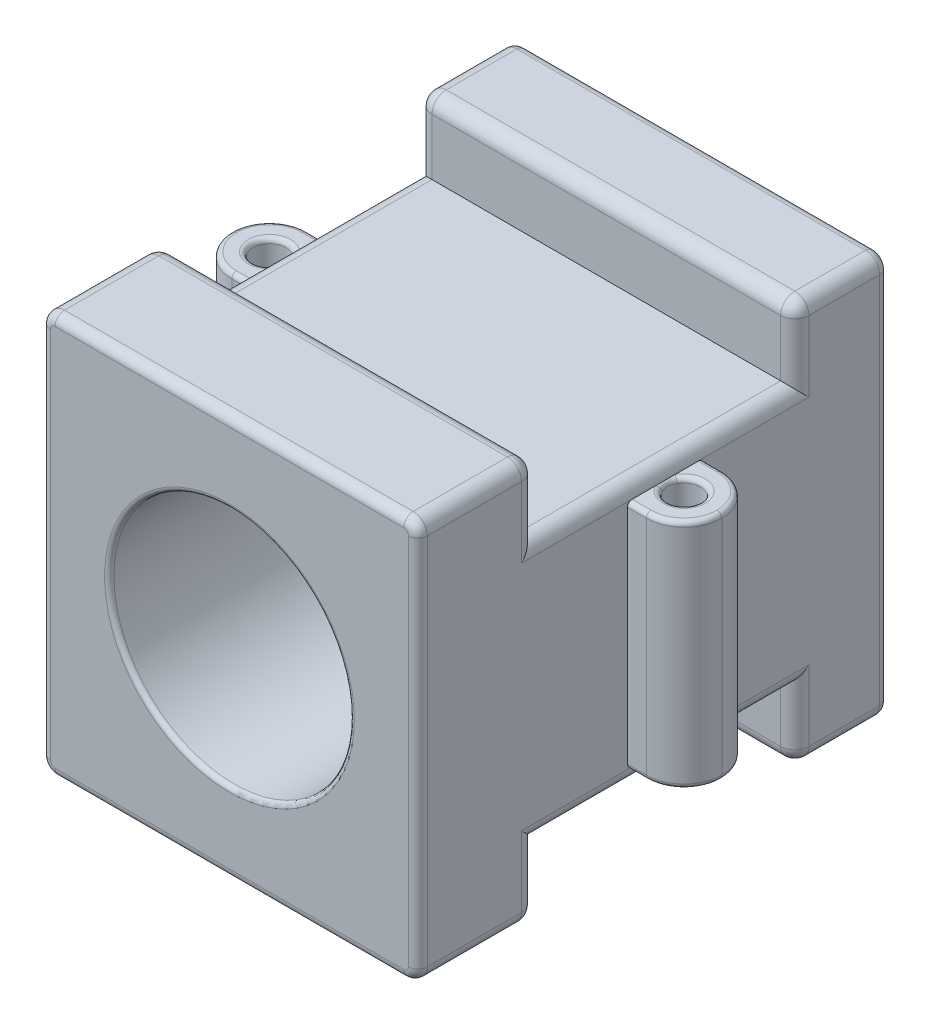
SolidWorks part; units mm, degrees
ref_plane "Plan de face" through (0, 0, 0) normal (0, 0, 1) x (1, 0, 0)
ref_plane "Plan de dessus" through (0, 0, 0) normal (0, 1, 0) x (1, 0, 0)
ref_plane "Plan de droite" through (0, 0, 0) normal (1, 0, 0) x (0, 0, -1)
sketch "Esquisse1" plane through (0, 0, 0) normal (0, 0, 1) x (1, 0, 0)
  line L1 (-40, 42.6) -> (40, 42.6)
  line L2 (-40, 42.6) -> (-40, -42.6)
  line L3 (-40, -42.6) -> (40, -42.6)
  line L4 (40, 42.6) -> (40, -42.6)
  line L5 (-40, 42.6) -> (40, -42.6) construction
  line L6 (-40, -42.6) -> (40, 42.6) construction
  point P0 (0, 0)
  dimension "D1" = 85.2
  dimension "D2" = 80
extrude "Boss.-Extru.1" add sketch "Esquisse1" along normal blind 100
sketch "Esquisse2" plane through (-40, 0, 0) normal (-1, 0, 0) x (0, 0, 1)
  line L0 (0, 0) -> (100, 0) construction
  line L1 (100, 42.6) -> (100, -42.6) construction
  line L2 (50, 0) -> (50, 42.6) construction
  line L3 (100, 42.6) -> (0, 42.6) construction
  line L4 (50, 42.6) -> (50, -42.6) construction
  line L5 (100, -42.6) -> (0, -42.6) construction
  line L6 (0, 42.6) -> (0, -42.6) construction
  line L7 (75, 42.6) -> (20, 42.6)
  line L8 (75, 42.6) -> (75, 27.6)
  line L9 (75, 27.6) -> (20, 27.6)
  line L10 (20, 42.6) -> (20, 27.6)
  line L12 (20, -42.6) -> (75, -42.6)
  line L13 (20, -42.6) -> (20, -27.6)
  line L14 (20, -27.6) -> (75, -27.6)
  line L15 (75, -42.6) -> (75, -27.6)
  dimension "D1" = 25
  dimension "D2" = 20
  dimension "D3" = 15
  dimension "D4" = 20
  dimension "D5" = 25
  dimension "D6" = 15
  dimension "D7" = 55
extrude "Enlèv. mat.-Extru.1" cut sketch "Esquisse2" against normal blind 100
fillet "Congé1" radius 3 4 edges at (0, -42.6, 75) (0, -42.6, 20) (0, 42.6, 75) (0, 42.6, 20)
fillet "Congé2" radius 2 4 edges at (40, 0, 0) (0, -42.6, 0) (-40, 0, 0) (0, 42.6, 0)
fillet "Congé3" radius 2 4 edges at (0, -42.6, 100) (-40, 0, 100) (0, 42.6, 100) (40, 0, 100)
fillet "Congé4" radius 3 36 edges at (-39.4142, -42.0142, 99.4142) (-39.4142, 42.0142, 99.4142) (39.4142, 42.0142, 99.4142) (39.4142, -42.0142, 99.4142) (-39.4142, -42.0142, 0.5858) (-39.4142, 42.0142, 0.5858) (39.4142, 42.0142, 0.5858) (39.4142, -42.0142, 0.5858) (40, -42.6, 9.5) (40, -41.7213, 19.1213) (40, 42.6, 9.5) (40, 41.7213, 19.1213) (-40, 42.6, 9.5) (-40, 41.7213, 19.1213) (-40, -42.6, 9.5) (-40, -41.7213, 19.1213) (40, -42.6, 88) (40, -41.7213, 75.8787) (40, 42.6, 88) (40, 41.7213, 75.8787) (-40, 42.6, 88) (-40, 41.7213, 75.8787) (-40, -42.6, 88) (-40, -41.7213, 75.8787) (40, -33.6, 20) (40, 33.6, 20) (40, 27.6, 47.5) (-40, 33.6, 20) (-40, -33.6, 20) (40, -27.6, 47.5) (40, -33.6, 75) (40, 33.6, 75) (-40, 33.6, 75) (-40, -33.6, 75) (-40, -27.6, 47.5) (-40, 27.6, 47.5)
sketch "Esquisse3" plane through (0, 0, 0) normal (0, 0, -1) x (-1, 0, 0)
  circle A0 centre (0, 0) radius 25.5
  dimension "D1" = 51
extrude "Enlèv. mat.-Extru.3" cut sketch "Esquisse3" against normal blind 100
sketch "Esquisse5" plane through (40, 0, 0) normal (1, 0, 0) x (0, 0, -1)
  line L1 (-78, 24.6) -> (-17, 24.6)
  line L2 (-78, 24.6) -> (-78, -24.6)
  line L3 (-78, -24.6) -> (-17, -24.6)
  line L4 (-17, 24.6) -> (-17, -24.6)
extrude "Boss.-Extru.2" add sketch "Esquisse5" along normal blind 20
sketch "Esquisse7" plane through (0, -24.6, 0) normal (0, -1, 0) x (1, 0, 0)
  line L0 (60, 78) -> (60, 17) construction
  line L1 (40, 78) -> (60, 78)
  line L2 (40, 78) -> (40, 68)
  line L3 (40, 68) -> (60, 68)
  line L4 (60, 78) -> (60, 68)
  line L5 (40, 78) -> (40, 17) construction
  line L6 (60, 17) -> (40, 17)
  line L7 (60, 17) -> (60, 27)
  line L8 (60, 27) -> (40, 27)
  line L9 (40, 17) -> (40, 27)
  dimension "D1" = 10
  dimension "D2" = 10
extrude "Enlèv. mat.-Extru.4" cut sketch "Esquisse7" against normal blind 60
sketch "Esquisse8" plane through (0, -24.6, 0) normal (0, -1, 0) x (1, 0, 0)
  line L0 (60, 27) -> (40, 27) construction
  line L1 (60, 68) -> (55, 68)
  line L2 (60, 68) -> (60, 27)
  line L3 (60, 27) -> (55, 27)
  line L4 (55, 68) -> (55, 27)
  dimension "D1" = 5
extrude "Enlèv. mat.-Extru.5" cut sketch "Esquisse8" against normal blind 78
fillet "Congé6" radius 20 2 edges at (55, 0, 27) (55, 0, 68)
sketch "Esquisse9" plane through (0, -24.6, 0) normal (0, -1, 0) x (1, 0, 0)
  line L0 (55, 47.5) -> (40, 47.5) construction
  line L1 (55, 48.6351) -> (55, 46.3649) construction
  line L2 (40, 68) -> (40, 27) construction
  line L3 (40, 68) -> (40, 55.5)
  line L4 (40, 55.5) -> (52, 55.5)
  line L5 (52, 55.5) -> (52, 39.5)
  line L6 (52, 39.5) -> (40, 39.5)
  line L7 (40, 39.5) -> (40, 27)
  line L8 (40, 27) -> (62.5234, 29.0461)
  line L9 (62.5234, 29.0461) -> (57.9649, 79.2245)
  line L10 (57.9649, 79.2245) -> (40, 68)
  circle A0 centre (44, 47.5) radius 3.5
  dimension "D1" = 7
  dimension "D2" = 4
  dimension "D4" = 8
  dimension "D3" = 8
  dimension "D5" = 8
extrude "Enlèv. mat.-Extru.7" cut sketch "Esquisse9" against normal blind 78
fillet "Congé7" radius 8 2 edges at (52, 0, 55.5) (52, 0, 39.5)
sketch "Esquisse10" plane through (-40, 0, 0) normal (-1, 0, 0) x (0, 0, 1)
  line L1 (17, 24.6) -> (78, 24.6)
  line L2 (17, 24.6) -> (17, -24.6)
  line L3 (17, -24.6) -> (78, -24.6)
  line L4 (78, 24.6) -> (78, -24.6)
extrude "Boss.-Extru.4" add sketch "Esquisse10" along normal blind 15
sketch "Esquisse13" plane through (0, 24.6, 0) normal (0, 1, 0) x (1, 0, 0)
  line L0 (-40, -78) -> (-40, -17) construction
  line L1 (-40, -39.5) -> (-52, -39.5)
  line L2 (-40, -39.5) -> (-40, -55.5)
  line L3 (-40, -55.5) -> (-52, -55.5)
  line L4 (-52, -39.5) -> (-52, -55.5)
  line L6 (-55, -78) -> (-40, -78) construction
  line L7 (-55, -17) -> (-40, -17) construction
  line L8 (-40, -55.5) -> (-40, -78)
  line L9 (-40, -78) -> (-110.7986, -93.3805)
  line L10 (-110.7986, -93.3805) -> (-110.7986, -4.487)
  line L11 (-110.7986, -4.487) -> (-52, -4.487)
  line L12 (-52, -4.487) -> (-40, -17)
  line L13 (-40, -17) -> (-40, -39.5)
  line L14 (-52, -39.5) -> (-52, -55.5)
  line L15 (-40, -55.5) -> (-40, -78)
  line L16 (-40, -39.5) -> (-52, -39.5)
  line M5 (-40, -78) -> (-40, -17)
  line M6 (-40, -17) -> (-55, -17)
  line M7 (-55, -17) -> (-55, -78)
  line M8 (-55, -78) -> (-40, -78)
  dimension "D1" = 16
  dimension "D2" = 12
  dimension "D3" = 22.5
  dimension "D4" = 22.5
extrude "Enlèv. mat.-Extru.9" cut sketch "Esquisse13" against normal blind 114 contours L12 L11 L10 L9 M8 M7 M6 | L4 L1 L3 M5 M6 M7 M8 region at (-46, 24.6, 38.8718) region at (-82.6088, 24.6, 45.3464)
fillet "Congé8" radius 8 2 edges at (-52, 0, 39.5) (-52, 0, 55.5)
sketch "Esquisse14" plane through (0, -24.6, 0) normal (0, -1, 0) x (1, 0, 0)
  line L0 (-52, 47.5) -> (-40, 47.5) construction
  line L1 (-40, 39.5) -> (-40, 55.5) construction
  circle A0 centre (-44, 47.5) radius 3.5
  dimension "D1" = 7
  dimension "D2" = 4
extrude "Enlèv. mat.-Extru.10" cut sketch "Esquisse14" against normal blind 114
fillet "Congé9" radius 1 20 edges at (47.5, 24.6, 47.5) (42, 24.6, 39.5) (49.6569, 24.6, 41.8431) (49.6569, 24.6, 53.1569) (42, 24.6, 55.5) (-42, 24.6, 55.5) (-42, 24.6, 39.5) (-49.6569, 24.6, 41.8431) (-49.6569, 24.6, 53.1569) (-40.5, 24.6, 47.5) (-40.5, -24.6, 47.5) (-42, -24.6, 55.5) (-49.6569, -24.6, 53.1569) (-49.6569, -24.6, 41.8431) (-42, -24.6, 39.5) (42, -24.6, 39.5) (49.6569, -24.6, 41.8431) (42, -24.6, 55.5) (49.6569, -24.6, 53.1569) (47.5, -24.6, 47.5)
fillet "Congé10" radius 1 2 edges at (-25.5, 0, 0) (-25.5, 0, 100)
